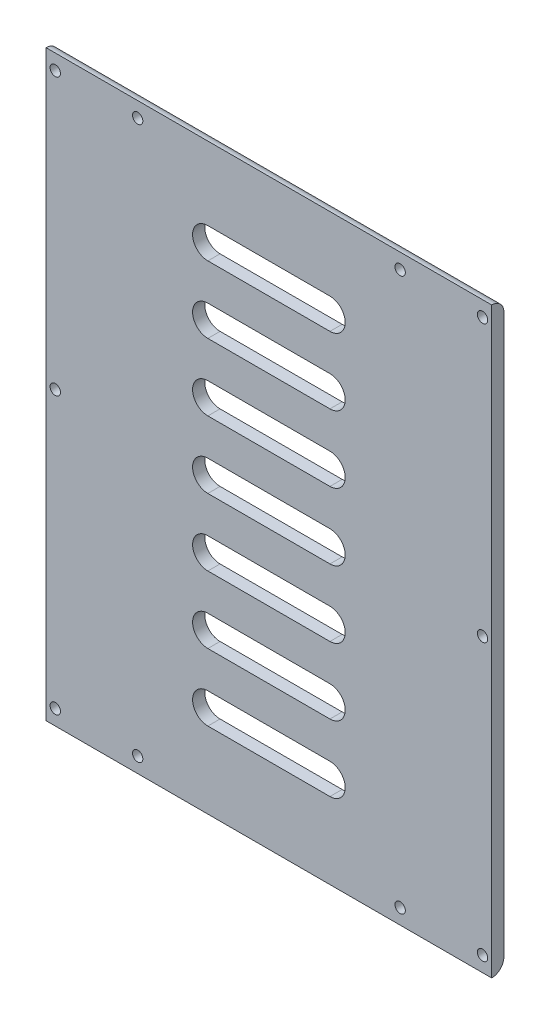
SolidWorks part; units mm, degrees
ref_plane "Front Plane" through (0, 0, 0) normal (1, 0, 0) x (0, 1, 0)
ref_plane "Top Plane" through (0, 0, 0) normal (0, 0, 1) x (0, 1, 0)
ref_plane "Right Plane" through (0, 0, 0) normal (0, 1, 0) x (-1, 0, 0)
sketch "Sketch1" plane through (0, 0, 0) normal (0, 0, 1) x (0, 1, 0)
  line L0 (95.5, 146) -> (95.5, 0) construction
  line L1 (0, 0) -> (191, 0)
  line L2 (0, 0) -> (0, 146)
  line L3 (0, 146) -> (191, 146)
  line L4 (191, 0) -> (191, 146)
  line L5 (30, 93) -> (30, 53) construction
  line L14 (35, 93) -> (35, 53)
  line L15 (25, 93) -> (25, 53)
  line L16 (0, 73) -> (191, 73) construction
  line L17 (52, 93) -> (52, 53) construction
  line L18 (57, 93) -> (57, 53)
  line L19 (47, 93) -> (47, 53)
  line L20 (74, 93) -> (74, 53) construction
  line L21 (79, 93) -> (79, 53)
  line L22 (69, 93) -> (69, 53)
  line L23 (96, 93) -> (96, 53) construction
  line L24 (101, 93) -> (101, 53)
  line L25 (91, 93) -> (91, 53)
  line L26 (118, 93) -> (118, 53) construction
  line L27 (123, 93) -> (123, 53)
  line L28 (113, 93) -> (113, 53)
  line L29 (140, 93) -> (140, 53) construction
  line L30 (145, 93) -> (145, 53)
  line L31 (135, 93) -> (135, 53)
  line L32 (162, 93) -> (162, 53) construction
  line L33 (167, 93) -> (167, 53)
  line L34 (157, 93) -> (157, 53)
  circle A0 centre (5, 3) radius 1.7
  circle A1 centre (5, 143) radius 1.7
  circle A2 centre (186, 143) radius 1.7
  circle A3 centre (186, 3) radius 1.7
  circle A4 centre (95.5, 143) radius 1.7
  circle A5 centre (95.5, 3) radius 1.7
  arc A6 (35, 93) -> (25, 93) centre (30, 93) ccw
  arc A7 (25, 53) -> (35, 53) centre (30, 53) ccw
  arc A8 (57, 93) -> (47, 93) centre (52, 93) ccw
  arc A9 (47, 53) -> (57, 53) centre (52, 53) ccw
  arc A10 (79, 93) -> (69, 93) centre (74, 93) ccw
  arc A11 (69, 53) -> (79, 53) centre (74, 53) ccw
  arc A12 (101, 93) -> (91, 93) centre (96, 93) ccw
  arc A13 (91, 53) -> (101, 53) centre (96, 53) ccw
  arc A14 (123, 93) -> (113, 93) centre (118, 93) ccw
  arc A15 (113, 53) -> (123, 53) centre (118, 53) ccw
  arc A16 (145, 93) -> (135, 93) centre (140, 93) ccw
  arc A17 (135, 53) -> (145, 53) centre (140, 53) ccw
  arc A18 (167, 93) -> (157, 93) centre (162, 93) ccw
  arc A19 (157, 53) -> (167, 53) centre (162, 53) ccw
  circle A20 centre (5, 30) radius 1.7
  circle A21 centre (186, 30) radius 1.7
  circle A22 centre (186, 116) radius 1.7
  circle A23 centre (5, 116) radius 1.7
  point P29 (30, 73)
  point P37 (0, 73)
  point P41 (52, 73)
  point P48 (74, 73)
  point P55 (96, 73)
  point P62 (118, 73)
  point P69 (140, 73)
  point P76 (162, 73)
  dimension "D7" = 3.4
  dimension "D1" = 191
  dimension "D2" = 146
  dimension "D3" = 3
  dimension "D4" = 5
  dimension "D5" = 3
  dimension "D6" = 5
  dimension "D13" = 10
  dimension "D14" = 40
  dimension "D16" = 12
  dimension "D8" = 25
  dimension "D15" = 7
extrude "Boss-Extrude2" add sketch "Sketch1" along normal blind 4
fillet "Fillet1" radius 4 2 edges at (-73, 191, 0) (-73, 0, 0)
equation "\"MotorDriverLength\"= 60mm"
equation "\"MotorLength\"= 60"
equation "\"MotorDriverWidth\"=45"
equation "\"MotorWidth\"= 37"
equation "\"InnerWallThickness\"=3"
equation "\"BatteryWidth\"= 60"
equation "\"OuterWallThickness\" = 6"
equation "\"CompartmentHeight\"=37"
equation "\"CompartmentWidth\"= \"MotorDriverLength\""
equation "\"MotorDiameter\"=37"
equation "\"BatteryHeight\"=24.2019"
equation "\"MotorDriverHeight\"=20"
equation "\"CircuitHeight\"=30"
equation "\"FanThickness\"= 10"
equation "\"FanHeight\"=50"
equation "\"MotorShaftHole\"=12"
equation "\"BearingBore\"=4"
equation "\"MinShinWidth\"= 20"
equation "\"ShinThickness\"=10"
equation "\"PivotDistance\"=40"
equation "\"ThighLength\"= 200"
equation "\"KneeLength\" =20"
equation "\"HipBore\"=27"
equation "\"ThighThickness\"=20"
equation "\"MaxBending\"=135"
equation "\"MaxStretchingAngle\"= 140"
equation "\"ThighJointDistance\"=157.485"
equation "\"ShinLength\"=100"
equation "\"BearingDiameter\"= 10"
equation "\"CircuitLength\"=50"
equation "\"ChessisInnerWidth\"= \"OuterWallThickness\" * 2 + \"MotorDriverLength\" * 2 + \"InnerWallThickness\" * 3 + \"CircuitLength\""
equation "\"D1@Sketch1\"=\"ChessisInnerWidth\""
equation "\"D2@Sketch1\"=\"MotorLength\"*2 + 20 +\"InnerWallThickness\"*2"
